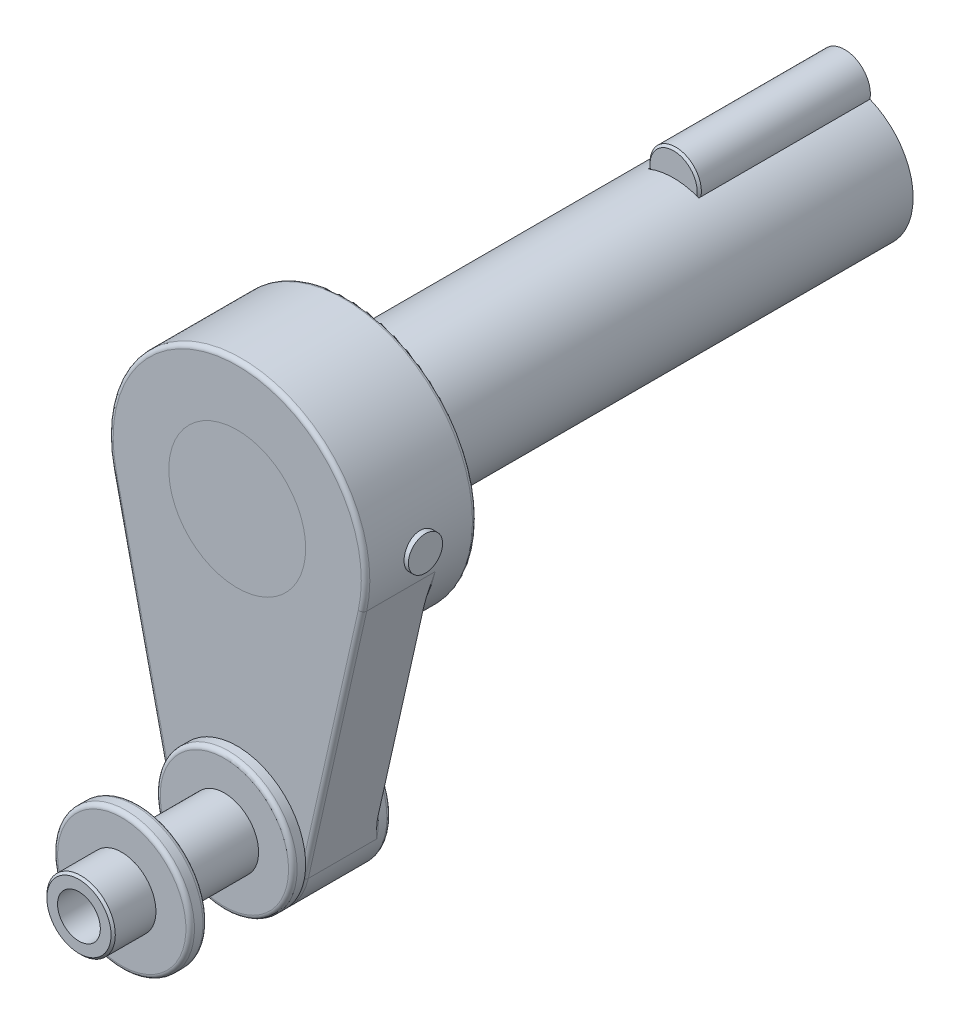
SolidWorks part; units mm, degrees
ref_plane "Front Plane" through (0, 0, 0) normal (0, 0, 1) x (1, 0, 0)
ref_plane "Top Plane" through (0, 0, 0) normal (0, 1, 0) x (1, 0, 0)
ref_plane "Right Plane" through (0, 0, 0) normal (1, 0, 0) x (0, 0, -1)
sketch "Sketch1" plane through (0, 0, 0) normal (0, 0, 1) x (1, 0, 0)
  line L0 (-14.6367, -3.2812) -> (-7.8062, -33.75)
  line L1 (14.6367, -3.2812) -> (7.8062, -33.75)
  circle A0 centre (0, 0) radius 15
  circle A1 centre (0, -32) radius 8
  circle A2 centre (0, 0) radius 8
  dimension "D1" = 30
  dimension "D2" = 16
  dimension "D3" = 16
  dimension "D4" = 32
extrude "Boss-Extrude1" add sketch "Sketch1" along normal blind 8 contours L0 A1 L1 A0 A2 | A1 L1 A0 L0 | A1 region at (0, -19.1018, 0) region at (-1.604, 14.4872, 0) region at (0, -32, 0)
extrude "Boss-Extrude2" add sketch "Sketch1<5>" against normal blind 5 contours A0 A2 region at (-1.604, 14.4872, 0)
sketch "Sketch1<5>" plane through (0, 0, 0) normal (0, 0, 1) x (1, 0, 0) same geometry as "Sketch1"
extrude "Boss-Extrude3" add sketch "Sketch1<7>" against normal blind 2 contours A1 region at (0, -32, 0)
sketch "Sketch1<7>" plane through (0, 0, 0) normal (0, 0, 1) x (1, 0, 0) same geometry as "Sketch1"
sketch "Sketch4" plane through (0, 0, 8) normal (0, 0, 1) x (1, 0, 0)
  point P0 (0, -32)
hole_wizard "M8x1.25 Tapped Hole1" positions "Sketch4" profile "Sketch5" tap size "M8x1.25" standard "ANSI Metric"
sketch "Sketch5" plane through (0, -32, 8) normal (1, 0, 0) x (0, -1, 0)
  line L0 (0, 0) -> (0, 21.7929)
  line L1 (0, 21.7929) -> (3.4, 19.75)
  line L2 (3.4, 19.75) -> (3.4, 0)
  line L5 (3.4, 0) -> (0, 0)
  line L10 (0, 21.7929) -> (-3.4, 19.75) construction
  line L11 (0, -6.35) -> (0, 107.95) construction
  dimension "Tap Drill Dia." = 6.8
  dimension "Tap Drill Depth" = 19.75
  dimension "Drill Angle" = 118
cosmetic thread "Hole Thread1" parameters "D1"=16, "D2"=8
sketch "Sketch7" plane through (0, 0, 8) normal (0, 0, 1) x (1, 0, 0)
  circle A0 centre (0, 0) radius 8
extrude "Boss-Extrude4" add sketch "Sketch7" against normal blind 71 separate body
sketch "Sketch6" plane through (0, 0, 0) normal (1, 0, 0) x (0, 0, -1)
  line L0 (5, 15) -> (-8, 15) construction
  circle A0 centre (-1.5, 0) radius 2
  point P2 (-1.5, 15)
  dimension "D1" = 4
extrude "Cut-Extrude1" cut sketch "Sketch6" against normal through all both and the other way through all
extrude "Boss-Extrude5" add sketch "Sketch6<2>" along normal mid plane 31 separate body
sketch "Sketch6<2>" plane through (0, 0, 0) normal (1, 0, 0) x (0, 0, -1) same geometry as "Sketch6"
sketch "Sketch8" plane through (0, 0, -63) normal (0, 0, -1) x (-1, 0, 0)
  circle A0 centre (0, 8) radius 3
  circle A2 centre (0, 0) radius 8 construction
  circle A3 centre (0, 0) radius 8 construction
  dimension "D1" = 6
extrude "Cut-Extrude2" cut sketch "Sketch8" against normal blind 20
extrude "Boss-Extrude6" add sketch "Sketch8<2>" against normal blind 20 separate body
sketch "Sketch8<2>" plane through (0, 0, -63) normal (0, 0, -1) x (-1, 0, 0) same geometry as "Sketch8"
chamfer "Chamfer1" distance 0.25 angle 45 1 edges at (-3, 8, -43)
sketch "Sketch9" plane through (0, 0, 0) normal (1, 0, 0) x (0, 0, -1)
  line L0 (2, -32) -> (-70.7418, -32) construction
  line L1 (2, -40) -> (2, -24) construction
  line L2 (2, -32) -> (2, -28)
  line L3 (2, -28) -> (-8, -28)
  line L4 (-8, -3.2812) -> (-8, -33.75) construction
  line L5 (-8, -28) -> (-8, -24)
  line L6 (-8, -24) -> (-9.5, -24)
  line L7 (-9.5, -24) -> (-9.5, -28)
  line L8 (-9.5, -28) -> (-19.5, -28)
  line L9 (-19.5, -28) -> (-19.5, -32)
  line L10 (-19.5, -32) -> (2, -32)
  dimension "D1" = 10
  dimension "D2" = 1.5
  dimension "D3" = 4
  dimension "D4" = 4
  dimension "D5" = 8
revolve "Revolve1" add sketch "Sketch9" angle 360 about L0
sketch "Sketch10" plane through (0, 0, 19.5) normal (0, 0, 1) x (1, 0, 0)
  point P0 (0, -32)
hole_wizard "M5x0.8 Tapped Hole1" positions "Sketch10" profile "Sketch11" tap size "M5x0.8" standard "ANSI Metric"
sketch "Sketch11" plane through (0, -32, 19.5) normal (1, 0, 0) x (0, -1, 0)
  line L0 (0, 0) -> (0, 7.2618)
  line L1 (0, 7.2618) -> (2.1, 6)
  line L2 (2.1, 6) -> (2.1, 0)
  line L5 (2.1, 0) -> (0, 0)
  line L10 (0, 7.2618) -> (-2.1, 6) construction
  line L11 (0, -6.35) -> (0, 107.95) construction
  dimension "Tap Drill Dia." = 4.2
  dimension "Tap Drill Depth" = 6
  dimension "Drill Angle" = 118
cosmetic thread "Hole Thread2" parameters "D1"=10, "D2"=5
sketch "Sketch12" plane through (0, 0, 0) normal (1, 0, 0) x (0, 0, -1)
  line L0 (-19.5, -32) -> (-52.446, -32) construction
  line L1 (-19.5, -28) -> (-19.5, -36) construction
  line L2 (-21.5, -29.5) -> (-21.5, -28)
  line L3 (-21.5, -28) -> (-26.5, -28)
  line L4 (-26.5, -28) -> (-26.5, -29.5)
  line L5 (-26.5, -29.5) -> (-21.5, -29.5)
  line L6 (-19.5, -29.5) -> (-19.5, -24)
  line L7 (-19.5, -24) -> (-21.5, -24)
  line L8 (-21.5, -24) -> (-21.5, -29.5)
  line L9 (-21.5, -29.5) -> (-19.5, -29.5)
  dimension "D2" = 8
  dimension "D3" = 5
  dimension "D4" = 2
  dimension "D5" = 5
  dimension "D6" = 16
revolve "Revolve2" add sketch "Sketch12" angle 360 about L0 region at (0, -26.75, 20.5)
revolve "Revolve3" add sketch "Sketch12<3>" angle 360 about L0 region at (0, -28.75, 24)
sketch "Sketch12<3>" plane through (0, 0, 0) normal (1, 0, 0) x (0, 0, -1) same geometry as "Sketch12"
fillet "Fillet1" radius 0.5 7 edges at (0, 15, 8) (-11.2215, -18.5156, 8) (0, -40, 8) (0, -24, 0) (0, -15, 0) (11.2215, -18.5156, 8) (15, 0, -5)
fillet "Fillet2" radius 0.5 1 edges at (-8, -32, 9.5)
fillet "Fillet3" radius 0.5 2 edges at (-8, -32, 19.5) (-8, -32, 21.5)
fillet "Fillet4" radius 0.5 1 edges at (8, -32, -2)
chamfer "Chamfer2" distance 0.25 angle 45 1 edges at (-4, -32, 26.5)
